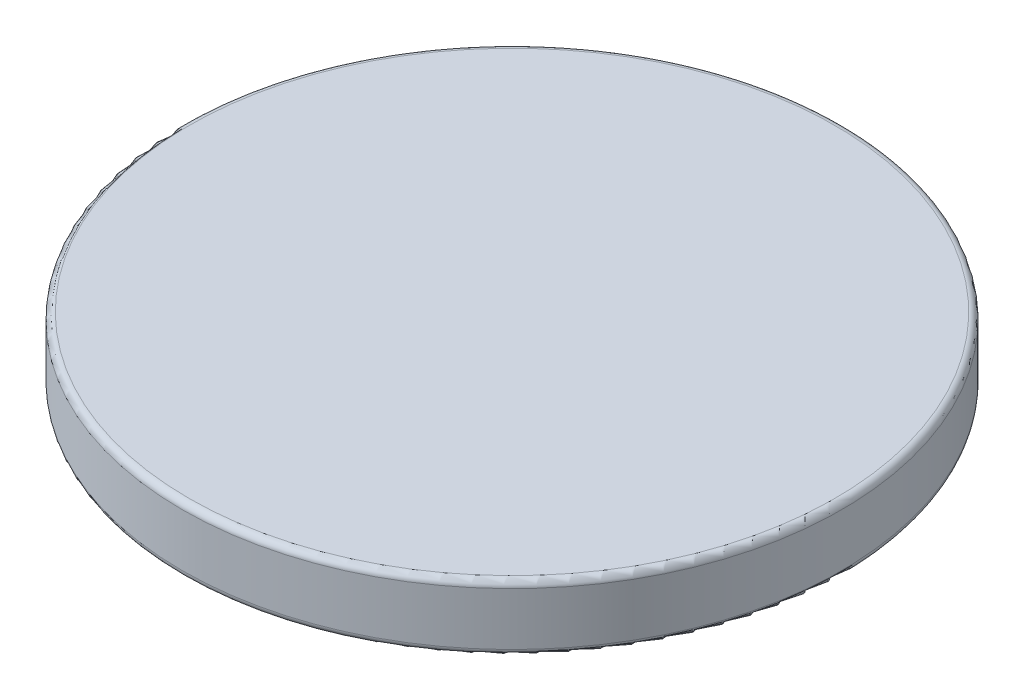
SolidWorks part; units mm, degrees
material "Ductile Iron"
ref_plane "Front Plane" through (0, 0, 0) normal (0, 0, 1) x (1, 0, 0)
ref_plane "Top Plane" through (0, 0, 0) normal (0, 1, 0) x (1, 0, 0)
ref_plane "Right Plane" through (0, 0, 0) normal (1, 0, 0) x (0, 0, -1)
ref_axis "CentralAxis" through (0, 1.1, 0) along (0, -1, 0)
sketch "BaseS" plane through (0, 0, 0) normal (0, 1, 0) x (1, 0, 0)
  circle A0 centre (0, 0) radius 10
  dimension "Diameter" = 20
extrude "Base" add sketch "BaseS" along normal mid plane 2
fillet "BaseFillet" radius 0.2 2 edges at (0, -1, 10) (0, 1, 10)
